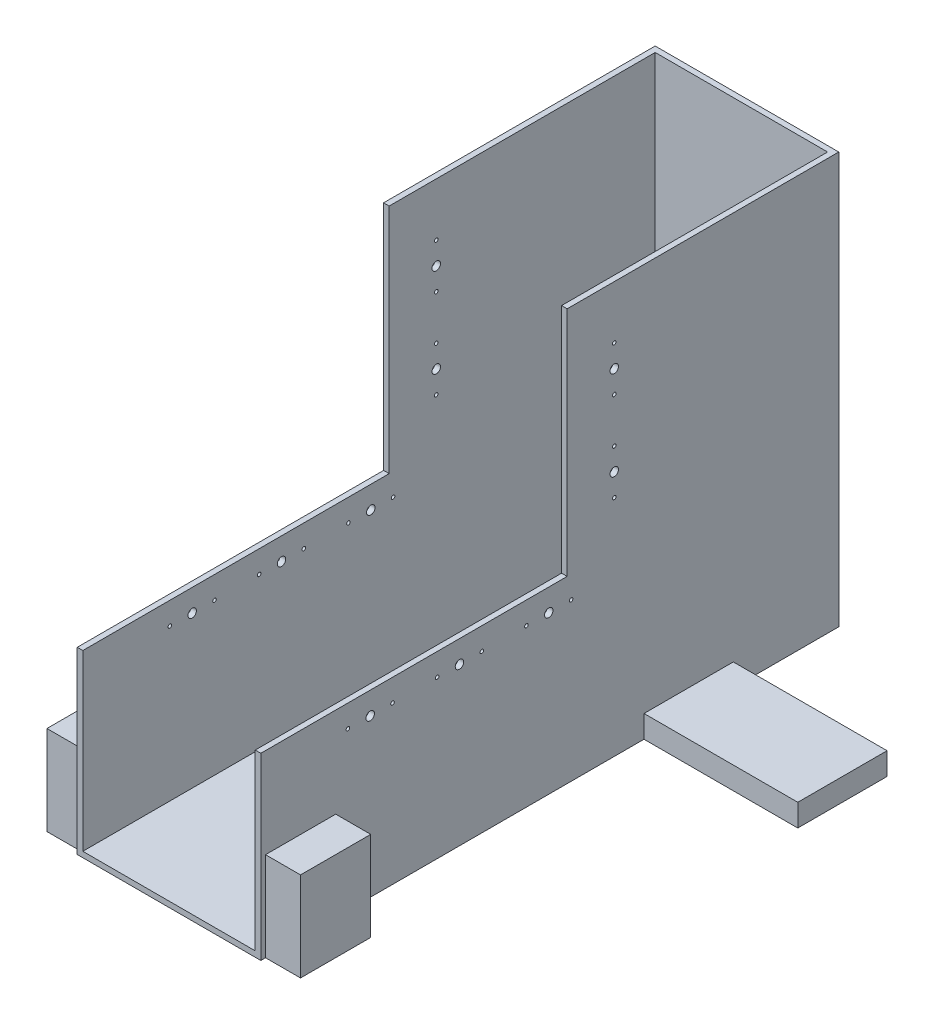
SolidWorks part; units mm, degrees
ref_plane "Front Plane" through (0, 0, 0) normal (0, 0, 1) x (1, 0, 0)
ref_plane "Top Plane" through (0, 0, 0) normal (0, 1, 0) x (1, 0, 0)
ref_plane "Right Plane" through (0, 0, 0) normal (1, 0, 0) x (0, 0, -1)
sketch "Sketch15" plane through (0, 0, 0) normal (1, 0, 0) x (0, 0, -1)
  line B0 (0, 0) -> (-657.6158, 0)
  line B1 (0, 0) -> (0, 467.9127)
  line B2 (-657.6158, 0) -> (-657.6158, 204.2049)
  line B3 (0, 467.9127) -> (-309.0338, 467.9127)
  line B4 (-309.0338, 204.2049) -> (-657.6158, 204.2049)
  line B5 (-309.0338, 204.2049) -> (-309.0338, 467.9127)
sketch_block_instance "frameSideview-1"
sketch_block "Block1"
extrude "Boss-Extrude1" add sketch "Sketch15" against normal blind 6.35
sketch "Sketch16" plane through (0, 0, 0) normal (0, 1, 0) x (1, 0, 0)
  line B0 (0, -685.8) -> (196.1896, -685.8)
  line B1 (0, -685.8) -> (0, 0)
  line B2 (196.1896, -685.8) -> (196.1896, 0)
  line B3 (0, -685.8) -> (196.1896, 0) construction
  line B4 (0, 0) -> (196.1896, -685.8) construction
sketch_block_instance "Drivebase_gearbox_Gap-1"
sketch_block "Drivebase_gearbox_Gap"
sketch "Sketch17" plane through (0, 0, 0) normal (0, 1, 0) x (1, 0, 0)
  line L0 (196.1896, -685.8) -> (196.1896, 0) construction
  line L1 (0, 0) -> (196.1896, 0)
  line L2 (0, 0) -> (0, -657.6158)
  line L3 (0, -657.6158) -> (196.1896, -657.6158)
  line L4 (196.1896, 0) -> (196.1896, -657.6158)
  line L5 (-6.35, -657.6158) -> (0, -657.6158) construction
extrude "Boss-Extrude2" add sketch "Sketch17" along normal blind 6.35
ref_plane "Plane1" through (98.0948, 0, 0) normal (1, 0, 0) x (0, 0, -1)
mirror "Mirror1" about plane through (98.0948, 0, 0) normal (1, 0, 0) of "Boss-Extrude1"
sketch "Sketch18" plane through (0, 0, 0) normal (0, 0, -1) x (-1, 0, 0)
  line L1 (-202.5396, 467.9127) -> (6.35, 467.9127)
  line L2 (-202.5396, 467.9127) -> (-202.5396, 0)
  line L3 (-202.5396, 0) -> (6.35, 0)
  line L4 (6.35, 467.9127) -> (6.35, 0)
extrude "Boss-Extrude3" add sketch "Sketch18" against normal blind 6.35
sketch "Sketch19" plane through (0, 0, 0) normal (0, 1, 0) x (1, 0, 0)
  line L1 (98.0948, -253.8595) -> (98.0948, 253.8595) construction
  line B0 (98.0948, -323.1859) -> (98.0948, 49676.8141) construction
  line B1 (-181.3052, -119.9859) -> (377.4948, -119.9859)
  line B2 (-181.3052, -119.9859) -> (-181.3052, -221.5859)
  line B3 (-181.3052, -221.5859) -> (377.4948, -221.5859)
  line B4 (377.4948, -119.9859) -> (377.4948, -221.5859)
  line B5 (-46.1772, -572.3724) -> (242.3668, -572.3724)
  line B6 (-46.1772, -572.3724) -> (-46.1772, -652.2613)
  line B7 (-46.1772, -652.2613) -> (242.3668, -652.2613)
  line B8 (242.3668, -572.3724) -> (242.3668, -652.2613)
sketch_block_instance "frameTopView-1"
sketch_block "frameTopView"
sketch "Sketch20" plane through (0, 0, 0) normal (0, 1, 0) x (1, 0, 0)
  line L0 (-181.3052, -119.9859) -> (377.4948, -119.9859) construction
  line L1 (-181.3052, -221.5859) -> (-6.35, -221.5859)
  line L2 (-181.3052, -221.5859) -> (-181.3052, -119.9859)
  line L3 (-181.3052, -119.9859) -> (-6.35, -119.9859)
  line L4 (-6.35, -221.5859) -> (-6.35, -119.9859)
  line L5 (-6.35, 0) -> (-6.35, -309.0338) construction
  line L6 (-181.3052, -221.5859) -> (377.4948, -221.5859) construction
  line L7 (377.4948, -119.9859) -> (202.5396, -119.9859)
  line L8 (377.4948, -119.9859) -> (377.4948, -221.5859)
  line L9 (377.4948, -221.5859) -> (202.5396, -221.5859)
  line L10 (202.5396, -119.9859) -> (202.5396, -221.5859)
  line L11 (202.5396, 0) -> (202.5396, -309.0338) construction
extrude "Boss-Extrude4" add sketch "Sketch20" along normal blind 25.4
sketch "Sketch22" plane through (0, 0, 0) normal (0, 1, 0) x (1, 0, 0)
  line L0 (-46.1772, -652.2613) -> (242.3668, -652.2613) construction
  line L1 (-46.1772, -572.3724) -> (-6.35, -572.3724)
  line L2 (-46.1772, -572.3724) -> (-46.1772, -652.2613)
  line L3 (-46.1772, -652.2613) -> (-6.35, -652.2613)
  line L4 (-6.35, -572.3724) -> (-6.35, -652.2613)
  line L5 (-6.35, -309.0338) -> (-6.35, -657.6158) construction
  line L6 (202.5396, -309.0338) -> (202.5396, -657.6158) construction
  line L7 (242.3668, -572.3724) -> (202.5396, -572.3724)
  line L8 (242.3668, -572.3724) -> (242.3668, -652.2613)
  line L9 (242.3668, -652.2613) -> (202.5396, -652.2613)
  line L10 (202.5396, -572.3724) -> (202.5396, -652.2613)
extrude "Boss-Extrude5" add sketch "Sketch22" along normal blind 101.6
sketch "Sketch25" plane through (-6.35, 0, 0) normal (-1, 0, 0) x (0, 0, 1)
  line L0 (255.4398, 467.9127) -> (255.4398, 0)
  line L1 (0, 467.9127) -> (309.0338, 467.9127) construction
  line L2 (572.3724, 0) -> (221.5859, 0) construction
  line L3 (0, 178.8049) -> (657.6158, 178.8049)
  line L4 (0, 0) -> (0, 467.9127) construction
  line L5 (657.6158, 204.2049) -> (657.6158, 0) construction
  line L6 (309.0338, 467.9127) -> (309.0338, 204.2049) construction
  line L7 (309.0338, 204.2049) -> (657.6158, 204.2049) construction
  circle A0 centre (533.1558, 178.8049) radius 4.826
  circle A1 centre (431.5558, 178.8049) radius 4.826
  circle A2 centre (329.9558, 178.8049) radius 4.826
  circle A3 centre (255.4398, 280.4607) radius 4.826
  circle A4 centre (255.4398, 382.0607) radius 4.826
  point P16 (255.4398, 280.4607)
  point P17 (255.4398, 467.9127)
  point P18 (255.4398, 382.0607)
  point P19 (329.9558, 178.8049)
  point P20 (431.5558, 178.8049)
  point P21 (533.1558, 178.8049)
  dimension "D8" = 9.652
  dimension "D9" = 9.652
  dimension "D10" = 9.652
  dimension "D11" = 9.652
  dimension "D12" = 9.652
  dimension "D1" = 53.594
  dimension "D2" = 25.4
  dimension "D3" = 85.852
  dimension "D4" = 101.6
  dimension "D5" = 124.46
  dimension "D6" = 101.6
  dimension "D7" = 101.6
extrude "Cut-Extrude1" cut sketch "Sketch25" against normal blind 6.35 contours A0 | A1 | A2 | A3 | A4
mirror "Mirror2" about plane through (98.0948, 0, 0) normal (1, 0, 0) of "Cut-Extrude1"
sketch "Sketch27" plane through (-6.35, 0, 0) normal (-1, 0, 0) x (0, 0, 1)
  line L0 (329.9558, 178.8049) -> (355.3558, 178.8049)
  line L1 (329.9558, 178.8049) -> (304.5558, 178.8049)
  circle A0 centre (330.0273, 183.5439) radius 0.0864
  circle A3 centre (355.3558, 178.8049) radius 2.032
  circle A4 centre (304.5558, 178.8049) radius 0.0352
  dimension "D3" = 4.064
  dimension "D4" = 0.0703
  dimension "D1" = 25.4
  dimension "D2" = 25.4
extrude "Cut-Extrude2" cut sketch "Sketch27" against normal blind 10.16 contours A4 | A3 region at (-6.35, 180.7794, 355.3558) region at (-6.35, 178.8049, 304.5216)
sketch "Sketch28" plane through (-6.35, 0, 0) normal (-1, 0, 0) x (0, 0, 1)
  line L0 (329.9558, 178.8049) -> (304.5558, 178.8049)
  circle A0 centre (304.5558, 178.8049) radius 2.032
  circle M2 centre (304.5558, 178.8049) radius 0.0352
  dimension "D2" = 4.064
  dimension "D1" = 25.4
extrude "Cut-Extrude3" cut sketch "Sketch28" against normal blind 14.732 contours A0 M2 region at (-6.35, 178.8049, 302.5812)
sketch "Sketch29" plane through (98.0948, 0, 0) normal (1, 0, 0) x (0, 0, -1)
  line L0 (-431.5558, 178.8049) -> (-456.9558, 178.8049)
  line L1 (-431.5558, 178.8049) -> (-406.1558, 178.8049)
  line L2 (-533.1558, 178.8049) -> (-558.5558, 178.8049)
  line L3 (-533.1558, 178.8049) -> (-507.7558, 178.8049)
  circle A0 centre (-406.1558, 178.8049) radius 2.032
  circle A1 centre (-456.9558, 178.8049) radius 2.032
  circle A2 centre (-507.7558, 178.8049) radius 2.032
  circle A3 centre (-558.5558, 178.8049) radius 2.032
  dimension "D3" = 4.064
  dimension "D1" = 25.4
  dimension "D2" = 25.4
  dimension "D4" = 25.4
  dimension "D5" = 25.4
extrude "Cut-Extrude4" cut sketch "Sketch29" against normal blind 144.272 contours A1 | A0 | A3 | A2
mirror "Mirror3" about plane through (98.0948, 0, 0) normal (1, 0, 0) of "Cut-Extrude3", "Cut-Extrude4", "Cut-Extrude2"
sketch "Sketch30" plane through (-6.35, 0, 0) normal (-1, 0, 0) x (0, 0, 1)
  line L0 (255.4398, 382.0607) -> (255.4398, 407.4607)
  line L1 (255.4398, 382.0607) -> (255.4398, 356.6607)
  line L2 (255.4398, 280.4607) -> (255.4398, 305.8607)
  line L3 (255.4398, 280.4607) -> (255.4398, 255.0607)
  circle A0 centre (255.4398, 356.6607) radius 2.032
  circle A1 centre (255.4398, 407.4607) radius 2.032
  circle A2 centre (255.4398, 305.8607) radius 2.032
  circle A3 centre (255.4398, 255.0607) radius 2.032
  dimension "D3" = 25.4
  dimension "D1" = 25.4
  dimension "D2" = 25.4
  dimension "D4" = 25.4
extrude "Cut-Extrude6" cut sketch "Sketch30" against normal blind 23.114 contours A1
extrude "Cut-Extrude7" cut sketch "Sketch30<6>" against normal blind 23.114 contours A0 | A3 | A2
sketch "Sketch30<6>" plane through (-6.35, 0, 0) normal (-1, 0, 0) x (0, 0, 1) same geometry as "Sketch30"
mirror "Mirror4" about plane through (98.0948, 0, 0) normal (1, 0, 0) of "Cut-Extrude7", "Cut-Extrude6"
sketch "Sketch34" plane through (0, 0, 0) normal (1, 0, 0) x (0, 0, -1)
  circle B0 centre (-558.5558, 178.8049) radius 2.032
  circle B1 centre (-533.1558, 178.8049) radius 4.826
  circle B2 centre (-507.7558, 178.8049) radius 2.032
  circle B3 centre (-456.9558, 178.8049) radius 2.032
  circle B4 centre (-431.5558, 178.8049) radius 4.826
  circle B5 centre (-406.1558, 178.8049) radius 2.032
  circle B6 centre (-355.3558, 178.8049) radius 2.032
  circle B7 centre (-329.9558, 178.8049) radius 4.826
  circle B8 centre (-304.5558, 178.8049) radius 2.032
  circle B9 centre (-255.4398, 305.8607) radius 2.032
  circle B10 centre (-255.4398, 280.4607) radius 4.826
  circle B11 centre (-255.4398, 255.0607) radius 2.032
  circle B12 centre (-255.4398, 382.0607) radius 4.826
  circle B13 centre (-255.4398, 407.4607) radius 2.032
  circle B14 centre (-255.4398, 356.6607) radius 2.032
sketch_block_instance "Block2-1"
sketch_block "Block2"
